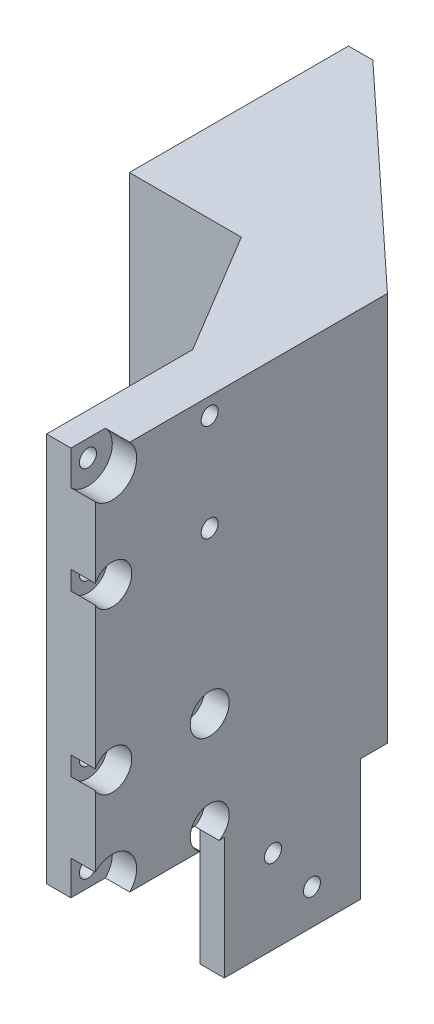
SolidWorks part; units mm, degrees
ref_plane "Plan de face" through (0, 0, 0) normal (0, 0, 1) x (1, 0, 0)
ref_plane "Plan de dessus" through (0, 0, 0) normal (0, 1, 0) x (1, 0, 0)
ref_plane "Plan de droite" through (0, 0, 0) normal (1, 0, 0) x (0, 0, -1)
sketch "Esquisse1" plane through (0, 0, 0) normal (0, 0, 1) x (1, 0, 0)
  line L1 (-33.3969, 24.3516) -> (14.6031, 24.3516)
  line L2 (-33.3969, 24.3516) -> (-33.3969, -55.6484)
  line L3 (-33.3969, -55.6484) -> (14.6031, -55.6484)
  line L4 (14.6031, 24.3516) -> (14.6031, -55.6484)
  dimension "D1" = 80
  dimension "D2" = 48
extrude "Boss.-Extru.1" add sketch "Esquisse1" along normal blind 5
sketch "Esquisse2" plane through (0, 0, 5) normal (0, 0, -1) x (-1, 0, 0)
  line L0 (-14.6031, 24.3516) -> (33.3969, 24.3516) construction
  line L1 (-14.6031, -55.6484) -> (-4.6031, -55.6484)
  line L2 (-14.6031, -55.6484) -> (-14.6031, 24.3516)
  line L3 (-14.6031, 24.3516) -> (-4.6031, 24.3516)
  line L4 (-4.6031, -55.6484) -> (-4.6031, 24.3516)
  dimension "D1" = 10
extrude "Boss.-Extru.2" add sketch "Esquisse2" against normal blind 55
sketch "Esquisse3" plane through (14.6031, 0, 0) normal (1, 0, 0) x (0, 0, -1)
  line L0 (-36.5, -52.1484) -> (-56.5, -52.1484) construction
  line L1 (-56.5, -52.1484) -> (-56.5, -32.1484) construction
  line L2 (-56.5, 20.8516) -> (-36.5, 20.8516) construction
  line L3 (-36.5, 20.8516) -> (-36.5, 0.8516) construction
  line L4 (-60, 24.3516) -> (-60, -55.6484) construction
  line L5 (-60, -55.6484) -> (0, -55.6484) construction
  line L6 (-60, 24.3516) -> (0, 24.3516) construction
  circle A0 centre (-56.5, -52.1484) radius 1.75
  circle A1 centre (-56.5, -32.1484) radius 1.75
  circle A2 centre (-36.5, -32.1484) radius 1.75
  circle A3 centre (-36.5, -52.1484) radius 1.75
  circle A4 centre (-56.5, 0.8516) radius 1.75
  circle A5 centre (-56.5, 20.8516) radius 1.75
  circle A6 centre (-36.5, 20.8516) radius 1.75
  circle A7 centre (-36.5, 0.8516) radius 1.75
  dimension "D1" = 3.5
  dimension "D2" = 20
  dimension "D3" = 3.5
  dimension "D4" = 3.5
  dimension "D5" = 3.5
extrude "Enlèv. mat.-Extru.1" cut sketch "Esquisse3" against normal up to next
sketch "Esquisse12" plane through (14.6031, 0, 0) normal (1, 0, 0) x (0, 0, -1)
  circle A2 centre (-36.5, -32.1484) radius 4
  circle A3 centre (-36.5, -52.1484) radius 4
  circle A4 centre (-56.5, 20.8516) radius 5
  circle A5 centre (-56.5, 0.8516) radius 4
  circle A6 centre (-56.5, -32.1484) radius 4
  circle A7 centre (-56.5, -52.1484) radius 5
  dimension "D1" = 10
  dimension "D2" = 8
extrude "Enlèv. mat.-Extru.6" cut sketch "Esquisse12" against normal blind 5
sketch "Esquisse4" plane through (0, 0, 0) normal (0, 0, -1) x (-1, 0, 0)
  line L0 (-14.6031, 24.3516) -> (33.3969, 24.3516) construction
  line L1 (33.3969, -55.6484) -> (28.3969, -55.6484)
  line L2 (33.3969, -55.6484) -> (33.3969, 24.3516)
  line L3 (33.3969, 24.3516) -> (28.3969, 24.3516)
  line L4 (28.3969, -55.6484) -> (28.3969, 24.3516)
  dimension "D1" = 5
extrude "Boss.-Extru.3" add sketch "Esquisse4" along normal blind 40
sketch "Esquisse5" plane through (-28.3969, 0, 0) normal (1, 0, 0) x (0, 0, -1)
  line L0 (40, -55.6484) -> (0, -55.6484) construction
  line L1 (40, 24.3516) -> (0, 24.3516) construction
  line L2 (40, -15.6484) -> (20, -15.6484) construction
  line L3 (40, 24.3516) -> (40, -55.6484) construction
  line L4 (20, -15.6484) -> (0, -15.6484) construction
  line L5 (0, 24.3516) -> (0, -55.6484) construction
  circle A0 centre (30, 14.3516) radius 2.75
  circle A1 centre (30, -5.6484) radius 2.75
  circle A2 centre (30, -25.6484) radius 2.75
  circle A3 centre (30, -45.6484) radius 2.75
  circle A4 centre (10, 14.3516) radius 2.75
  circle A5 centre (10, -5.6484) radius 2.75
  circle A6 centre (10, -25.6484) radius 2.75
  circle A7 centre (10, -45.6484) radius 2.75
  point P12 (20, 24.3516)
  point P22 (30, -15.6484)
  point P29 (0, 0)
  point P30 (0, 0)
  point P31 (0, 0)
  point P32 (0, 0)
  point P33 (0, 0)
  point P34 (10, -15.6484)
  dimension "D1" = 5.5
  dimension "D2" = 10
  dimension "D3" = 10
  dimension "D4" = 20
  dimension "D5" = 20
extrude "Enlèv. mat.-Extru.2" cut sketch "Esquisse5" against normal up to next
sketch "Esquisse7" plane through (0, 24.3516, 0) normal (0, 1, 0) x (1, 0, 0)
  line L0 (14.6031, 0) -> (-28.3969, 40)
  line L1 (-28.3969, 40) -> (-28.3969, 0)
  line L2 (-28.3969, 40) -> (-28.3969, 0) construction
  line L4 (14.6031, 0) -> (-28.3969, 0) construction
  line L5 (-28.3969, 0) -> (14.6031, 0)
  point P4 (-28.3969, 0)
  point P11 (-28.3969, -0.5791)
extrude "Boss.-Extru.4" add sketch "Esquisse7" against normal up to surface (80 mm away) up to face at (-1.254, -55.6484, 21.5613)
ref_plane "Plan1" through (-28.3969, 0, 0) normal (-1, 0, 0) x (0, 0, 1)
sketch "Esquisse8" plane through (-28.3969, 0, 0) normal (-1, 0, 0) x (0, 0, 1)
  circle A0 centre (-30, -45.6484) radius 6
  circle A1 centre (-30, -25.6484) radius 6
  circle A2 centre (-30, -5.6484) radius 6
  circle A3 centre (-30, 14.3516) radius 6
  circle A4 centre (-10, -45.6484) radius 6
  circle A5 centre (-10, -25.6484) radius 6
  circle A6 centre (-10, -5.6484) radius 6
  circle A7 centre (-10, 14.3516) radius 6
  dimension "D1" = 12
extrude "Enlèv. mat.-Extru.4" cut sketch "Esquisse8" against normal up to next
chamfer "Chanfrein2" distance 25 distance2 15 1 edges at (4.6031, -15.6484, 5) first distance on face at (4.6031, 0.8516, 58.25)
sketch "Esquisse10" plane through (0, -55.6484, 0) normal (0, -1, 0) x (1, 0, 0)
  line L0 (14.6031, 34.5635) -> (14.6031, 0) construction
  line L1 (14.6031, 33.5) -> (9.6031, 33.5)
  line L2 (14.6031, 33.5) -> (14.6031, 5.5)
  line L3 (14.6031, 5.5) -> (9.6031, 5.5)
  line L4 (9.6031, 33.5) -> (9.6031, 5.5)
  line L5 (9.6031, 60) -> (4.6031, 60) construction
  dimension "D1" = 28
  dimension "D2" = 26.5
  dimension "D3" = 5
extrude "Boss.-Extru.5" add sketch "Esquisse10" along normal blind 25
sketch "Esquisse11" plane through (4.6031, 0, 0) normal (-1, 0, 0) x (0, 0, 1)
  line L0 (15.5, -73.4293) -> (23.5, -73.4293) construction
  line L1 (23.5, -73.4293) -> (23.5, -63.4293) construction
  line L2 (33.5, -80.6484) -> (5.5, -80.6484) construction
  circle A0 centre (15.5, -73.4293) radius 1.75
  circle A1 centre (23.5, -63.4293) radius 1.75
  point P7 (19.5, -80.6484)
  point P8 (19.5, -73.4293)
  dimension "D1" = 3.5
  dimension "D2" = 10
  dimension "D3" = 8
extrude "Enlèv. mat.-Extru.5" cut sketch "Esquisse11" against normal up to next
sketch "Esquisse13" plane through (-33.3969, 0, 0) normal (-1, 0, 0) x (0, 0, 1)
  line L1 (-40, -55.6484) -> (5.0553, -55.6484)
  line L2 (-40, -55.6484) -> (-40, 24.3516)
  line L3 (-40, 24.3516) -> (5.0553, 24.3516)
  line L4 (5.0553, -55.6484) -> (5.0553, 24.3516)
